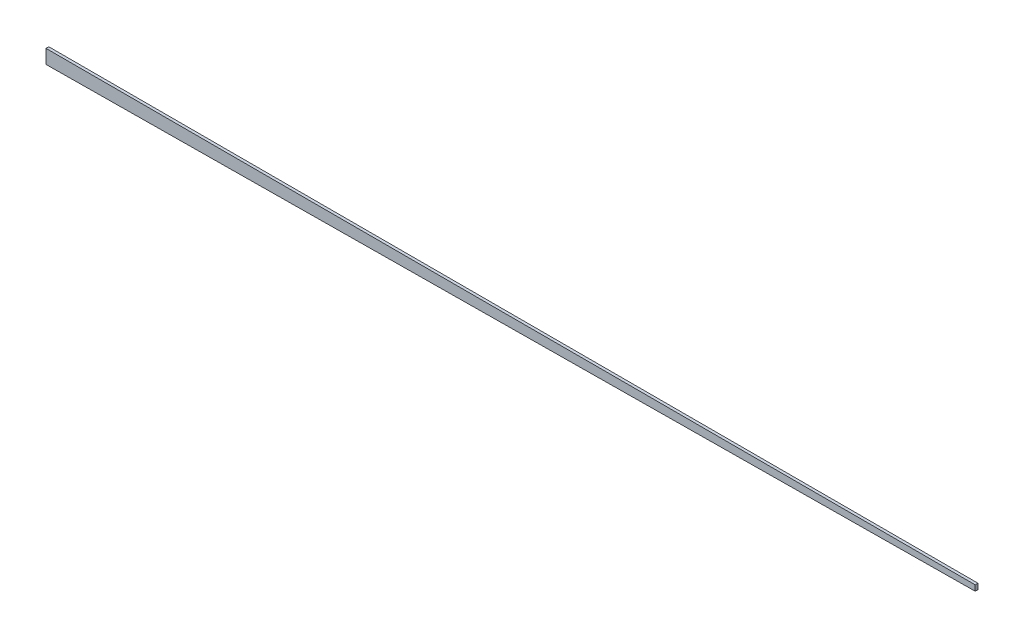
SolidWorks part; units mm, degrees
ref_plane "Front Plane" through (0, 0, 0) normal (0, 0, 1) x (1, 0, 0)
ref_plane "Top Plane" through (0, 0, 0) normal (0, 1, 0) x (1, 0, 0)
ref_plane "Right Plane" through (0, 0, 0) normal (1, 0, 0) x (0, 0, -1)
sketch "Sketch1" plane through (0, 0, 0) normal (0, 0, 1) x (1, 0, 0)
  line L0 (0, 0) -> (1000, 9)
  line L1 (1000, 9) -> (1000, 15)
  line L2 (1000, 15) -> (0, 15)
  line L3 (0, 15) -> (0, 0)
  dimension "D1" = 1000
  dimension "D2" = 15
  dimension "D3" = 6
extrude "Boss-Extrude1" add sketch "Sketch1" along normal blind 3 contours L0 L1 L2 L3
